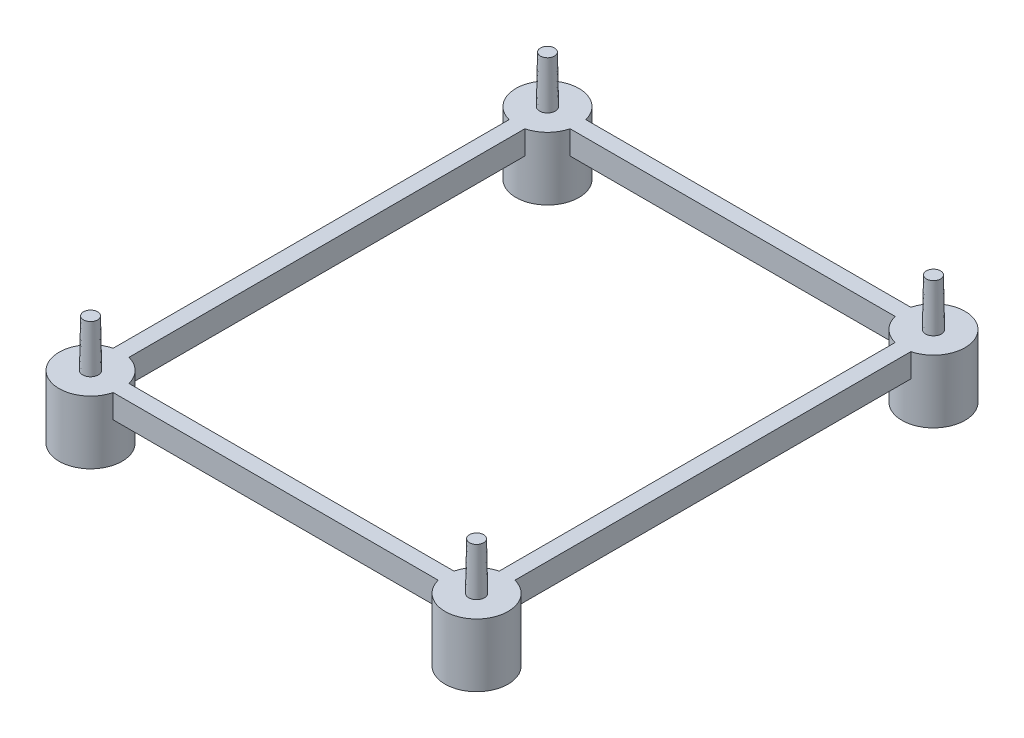
SolidWorks part; units mm, degrees
ref_plane "Front Plane" through (0, 0, 0) normal (0, 0, 1) x (1, 0, 0)
ref_plane "Top Plane" through (0, 0, 0) normal (0, 1, 0) x (1, 0, 0)
ref_plane "Right Plane" through (0, 0, 0) normal (1, 0, 0) x (0, 0, -1)
sketch "Sketch1" plane through (0, 0, 0) normal (0, 1, 0) x (1, 0, 0)
  line L0 (3.5, 80) -> (52.5, 80) construction
  line L1 (0, 0) -> (56, 0)
  line L2 (0, 0) -> (0, 85)
  line L3 (0, 85) -> (56, 85)
  line L4 (56, 0) -> (56, 85)
  line L5 (3.5, 22) -> (52.5, 22) construction
  line L6 (52.5, 22) -> (52.5, 80) construction
  line L7 (2.5, 80) -> (2.5, 22)
  line L8 (3.5, 21) -> (52.5, 21)
  line L9 (53.5, 22) -> (53.5, 80)
  line L10 (3.5, 81) -> (52.5, 81)
  line L11 (3.5, 79) -> (52.5, 79)
  line L12 (4.5, 22) -> (4.5, 80)
  line L13 (51.5, 80) -> (51.5, 22)
  line L14 (3.5, 23) -> (52.5, 23)
  circle A0 centre (3.5, 80) radius 1
  circle A1 centre (52.5, 80) radius 1
  circle A2 centre (3.5, 22) radius 1
  circle A3 centre (52.5, 22) radius 1
  point P29 (4.5, 22)
  point P30 (4.5, 80)
  point P31 (4.5, 80)
  dimension "D6" = 2
  dimension "D7" = 3.5
  dimension "D8" = 5
  dimension "D1" = 56
  dimension "D2" = 85
  dimension "D3" = 49
  dimension "D4" = 49
  dimension "D5" = 58
extrude "Boss-Extrude1" add sketch "Sketch1" along normal blind 3 contours A2 L14 L12 L11 A0 L7 | A1 L10 A0 L12 L11 L13 | A3 L13 L14 L12 A2 L8 | A3 L9 A1 L11 L13 L14 | A1 | A1 L13 L11 | A3 | A3 L14 L13 | A2 | A2 L12 L14 | A0 L11 L12 | A0 region at (3.497, 0, -51) region at (3.5, 0, -80) region at (3.5, 0, -22) region at (28, 0, -80.0035) region at (4.2766, 0, -79.2234) region at (4.2766, 0, -22.7766) region at (28, 0, -21.9965) region at (52.5, 0, -80) region at (52.5, 0, -22) region at (52.503, 0, -51) region at (51.7234, 0, -79.2234) region at (51.7234, 0, -22.7766)
sketch "Sketch2" plane through (0, 3, 0) normal (0, 1, 0) x (1, 0, 0)
  circle A0 centre (3.5, 80) radius 1
  circle A1 centre (52.5, 80) radius 1
  circle A2 centre (52.5, 22) radius 1
  circle A3 centre (3.5, 22) radius 1
  dimension "D1" = 2
extrude "Boss-Extrude2" add sketch "Sketch2" along normal blind 6 draft 1
sketch "Sketch3" plane through (0, 0, 0) normal (0, -1, 0) x (1, 0, 0)
  circle A0 centre (3.5, -22) radius 4
  circle A1 centre (52.5, -22) radius 4
  circle A2 centre (52.5, -80) radius 4
  circle A3 centre (3.5, -80) radius 4
  dimension "D1" = 8
extrude "Boss-Extrude3" add sketch "Sketch3" along normal blind 5 and the other way blind 3
sketch "Sketch4" plane through (0, -5, 0) normal (0, -1, 0) x (1, 0, 0)
  circle A0 centre (3.5, -22) radius 3.1
  circle A1 centre (52.5, -22) radius 3.1
  circle A2 centre (3.5, -80) radius 3.1
  circle A3 centre (52.5, -80) radius 3.1
  dimension "D1" = 6.2
extrude "Cut-Extrude1" cut sketch "Sketch4" against normal blind 4
